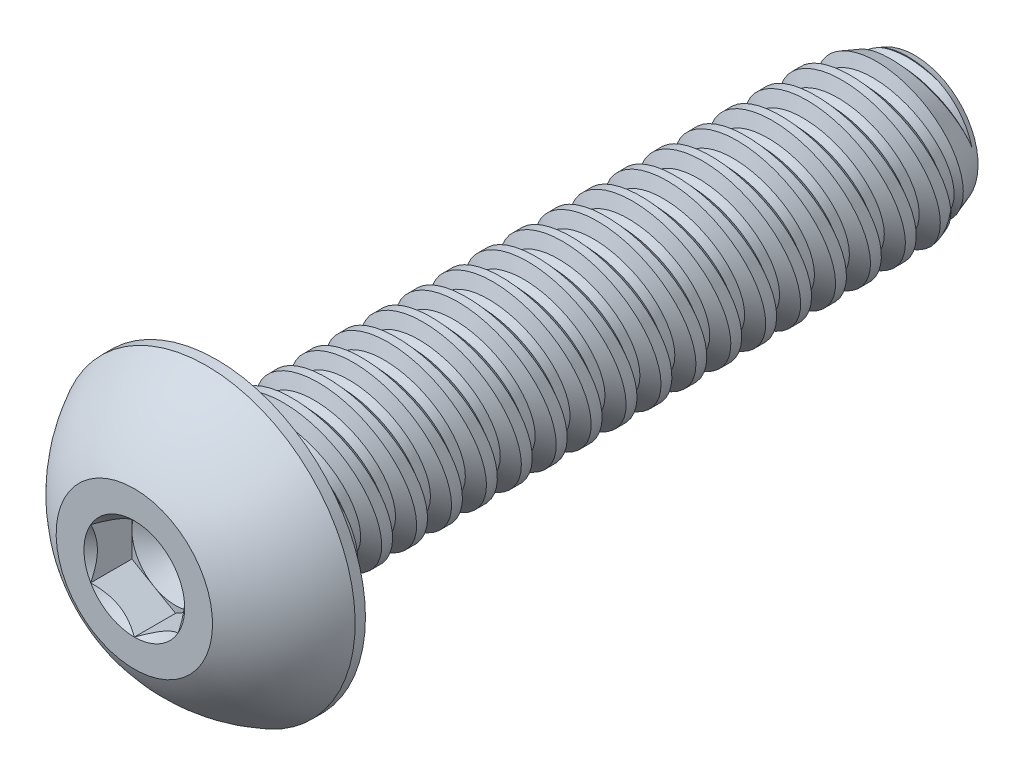
SolidWorks part; units mm, degrees
material "Alloy Steel"
ref_plane "Front" through (0, 0, 0) normal (0, 0, 1) x (1, 0, 0)
ref_plane "Top" through (0, 0, 0) normal (0, 1, 0) x (1, 0, 0)
ref_plane "Right" through (0, 0, 0) normal (1, 0, 0) x (0, 0, -1)
sketch "Sketch1" plane through (0, 0, 0) normal (1, 0, 0) x (0, 0, -1)
  line L0 (0, 0) -> (-1.4986, 0) construction
  line L1 (0, 0) -> (12.7, 0)
  line L2 (0, 0) -> (0, 1.4224)
  line L3 (0, 1.4224) -> (12.7, 1.4224)
  line L4 (12.7, 0) -> (12.7, 1.4224)
  line L5 (0, -1.4224) -> (12.7, -1.4224) construction
  dimension "D1" = 12.7
  dimension "Thread Dia" = 2.8448
  dimension "Length" = 12.7
  dimension "Head Height" = 1.4986
revolve "Revolve1" add sketch "Sketch1" angle 360 about L0
ref_plane "Plane1" through (0, 0, 1.4986) normal (0, 0, 1) x (1, 0, 0)
sketch "Sketch2" plane through (0, 0, 0) normal (1, 0, 0) x (0, 0, -1)
  line L0 (0, 1.4224) -> (0, -1.4224) construction
  line L1 (0, -1.4224) -> (0.635, -1.4224) construction
  line L2 (0.635, -1.4224) -> (0, 1.4224) construction
  line L3 (0, 1.4224) -> (0.0775, 1.4397) construction
  line L4 (0.0775, 1.4397) -> (0.6197, 1.5607)
  line L5 (0.6197, 1.5607) -> (0.501, 1.1821)
  line L6 (0.501, 1.1821) -> (0.346, 1.1475)
  line L7 (0.346, 1.1475) -> (0.0775, 1.4397)
  line L8 (0.4235, 1.1648) -> (0.3486, 1.5002) construction
  line L9 (0, -1.4224) -> (12.7, -1.4224) construction
  line L10 (0, 1.4224) -> (12.7, 1.4224) construction
  line L12 (0.366, 1.4224) -> (1.001, -1.4224) construction
  line L13 (0, -0.1526) -> (1.367, 0.1526) construction
  line L15 (0, 0) -> (0, 1.4224) construction
  point P19 (0.6835, 0)
  dimension "D1" = 60
  dimension "Thread Pitch" = 0.635
  dimension "D2" = 0.0794
  dimension "D3" = 0.1588
  dimension "D4" = 0.635
revolve "Cut-Revolve1" cut sketch "Sketch2" angle 360 about L13
sketch "Sketch3" plane through (0, 0, 0) normal (1, 0, 0) x (0, 0, -1)
  line L0 (12.7, 1.1475) -> (11.9446, 1.4224)
  line L1 (11.9446, 1.4224) -> (12.7, 1.4224)
  line L2 (12.7, 1.4224) -> (12.7, 1.1475)
  line L3 (0, 1.4224) -> (12.7, 1.4224) construction
  line L4 (12.7, 0) -> (12.7, 1.4224) construction
  line L5 (11.9446, 0) -> (0, 0) construction
  line L6 (11.9446, 1.4224) -> (11.9446, -1.4224) construction
  line L7 (0, -1.4224) -> (12.7, -1.4224) construction
  dimension "D1" = 20
  dimension "D2" = 2.8448
revolve "Cut-Revolve2" cut sketch "Sketch3" angle 360 about L5
pattern_linear "LPattern1" count 20 spacing 0.635 along (0, 0, 1)
pattern_linear "LPattern2" count 2 spacing 0.635 along (0, 0, 1)
sketch "Sketch4" plane through (0, 0, 0) normal (0, 0, 1) x (1, 0, 0)
  circle A0 centre (0, 0) radius 2.7051
  dimension "Head Dia" = 5.4102
extrude "Extrude1" add sketch "Sketch4" along normal up to surface (1.4986 mm away)
sketch "Sketch9" plane through (0, 0, 0) normal (1, 0, 0) x (0, 0, -1)
  line L0 (0, 2.7051) -> (-0.1873, 2.7051)
  line L1 (0, 2.7051) -> (0, 2.8924)
  line L2 (0, 2.8924) -> (-1.6859, 2.8924)
  line L3 (0, 0) -> (-1.4986, 0) construction
  line L4 (-1.6859, 2.8924) -> (-1.6859, 1.4224)
  line L5 (-1.6859, 1.4224) -> (-1.4986, 1.4224)
  line L6 (0, 0) -> (0, 1.4224) construction
  line L10 (0, 2.7051) -> (-1.4986, 2.7051) construction
  line L11 (0, 1.4224) -> (12.7, 1.4224) construction
  line L12 (-1.4986, 2.7051) -> (-1.4986, -2.7051) construction
  arc A0 (-1.4986, 1.4224) -> (-0.1873, 2.7051) centre (1.1758, 0) cw
  dimension "Side Head Height" = 0.1873
revolve "Cut-Revolve3" cut sketch "Sketch9" angle 360 about L3
sketch "Sketch6" plane through (0, 0, 1.4986) normal (0, 0, 1) x (1, 0, 0)
  line L1 (0, -0.9165) -> (0.7937, -0.4583)
  line L2 (0.7937, -0.4583) -> (0.7937, 0.4583)
  line L3 (0.7937, 0.4583) -> (0, 0.9165)
  line L4 (0, 0.9165) -> (-0.7938, 0.4583)
  line L5 (-0.7938, 0.4583) -> (-0.7938, -0.4583)
  line L6 (-0.7938, -0.4583) -> (0, -0.9165)
  circle A0 centre (0, 0) radius 0.7938 construction
  dimension "Hex" = 1.5875
extrude "Cut-Extrude1" cut sketch "Sketch6" against normal blind 0.7493
sketch "Sketch7" plane through (0, 0, 1.4986) normal (0, 0, 1) x (1, 0, 0)
  circle A0 centre (0, 0) radius 0.9165
extrude "Cut-Extrude4" cut sketch "Sketch7" against normal blind 0.7493 draft 45
sketch "Sketch8" plane through (0, 0, 0.7493) normal (0, 0, 1) x (1, 0, 0)
  circle A0 centre (0, 0) radius 0.7938 construction
  circle A1 centre (0, 0) radius 0.7938
extrude "Cut-Extrude5" cut sketch "Sketch8" against normal blind 0.2498 draft 60
equation "\"D2@Sketch2\"=\"Thread Pitch@Sketch2\"/8"
equation "\"D3@Sketch2\"=\"Thread Pitch@Sketch2\"/4"
equation "\"D4@Sketch2\"=\"Thread Pitch@Sketch2\""
equation "\"D3@LPattern1\"=\"Thread Pitch@Sketch2\""
equation "\"D1@Cut-Extrude1\"=\"Head Height@Sketch1\"/2"
equation "\"D1@Cut-Extrude4\"=\"D1@Cut-Extrude1\""
equation "\"D1@Cut-Extrude5\"=\"D1@Cut-Extrude1\"/3"
equation "\"D1@LPattern1\"=\"D1@Sketch1\"/\"Thread Pitch@Sketch2\""
equation "\"D3@LPattern2\"=\"Thread Pitch@Sketch2\""
equation "\"Side Head Height@Sketch9\"=\"Head Height@Sketch1\"/8"
